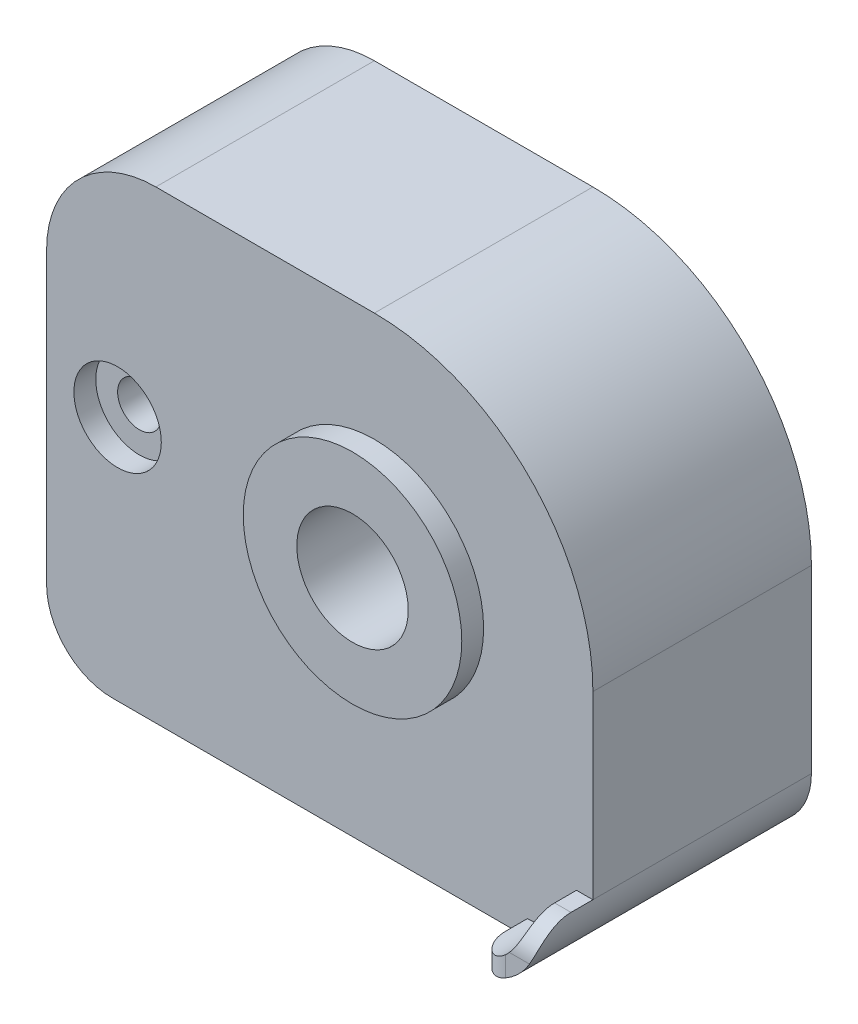
SolidWorks part; units mm, degrees
ref_plane "Plan de face" through (0, 0, 0) normal (0, 0, 1) x (1, 0, 0)
ref_plane "Plan de dessus" through (0, 0, 0) normal (0, 1, 0) x (1, 0, 0)
ref_plane "Plan de droite" through (0, 0, 0) normal (1, 0, 0) x (0, 0, -1)
sketch "Esquisse1" plane through (0, 0, 0) normal (0, 0, 1) x (1, 0, 0)
  line L0 (0, 20) -> (-30, 20)
  line L1 (-30, 20) -> (-30, -20)
  line L2 (-30, -20) -> (0, -20)
  line L3 (20, 0) -> (-30, 0) construction
  arc A0 (0, -20) -> (0, 20) centre (0, 0) ccw
  circle A1 centre (0, 0) radius 5.2
  circle A2 centre (-23.5, 0) radius 2
  circle A3 centre (-23.5, 0) radius 4
  dimension "D2" = 4
  dimension "D4" = 10.4
  dimension "D6" = 8
  dimension "D1" = 40
  dimension "D3" = 30
  dimension "D5" = 6.5
extrude "Boss.-Extru.1" add sketch "Esquisse1" along normal blind 20 contours L2 A0 L0 L1
sketch "Esquisse3" plane through (-30, 0, 0) normal (-1, 0, 0) x (0, 0, 1)
  line L0 (0, 0) -> (20, 0) construction
  line L1 (20, 20) -> (20, -20) construction
  circle A0 centre (10, 0) radius 5
  dimension "D1" = 10
  dimension "D2" = 10
extrude "Enlèv. mat.-Extru.1" cut sketch "Esquisse3" against normal blind 20
fillet "Congé1" radius 10 2 edges at (-30, 20, 10) (-30, -20, 10)
extrude "Enlèv. mat.-Extru.3" cut sketch "Esquisse1<4>" against normal through all and the other way through all contours A2
sketch "Esquisse1<4>" plane through (0, 0, 0) normal (0, 0, 1) x (1, 0, 0) same geometry as "Esquisse1"
extrude "Enlèv. mat.-Extru.4" cut sketch "Esquisse1<5>" along normal blind 2 contours A3
sketch "Esquisse1<5>" plane through (0, 0, 0) normal (0, 0, 1) x (1, 0, 0) same geometry as "Esquisse1"
extrude "Enlèv. mat.-Extru.5" cut sketch "Esquisse1<6>" against normal blind 2 from surface contours A3 starting at face at (-21.5, 0, 20)
sketch "Esquisse1<6>" plane through (0, 0, 0) normal (0, 0, 1) x (1, 0, 0) same geometry as "Esquisse1"
sketch "Esquisse5" plane through (0, 0, 20) normal (0, 0, 1) x (1, 0, 0)
  line L9 (20, 0) -> (20, -16.5)
  line L10 (14, -22.5) -> (-24, -22.5)
  line L11 (-30, -16.5) -> (-30, -10)
  line L12 (-20, -20) -> (0, -20)
  arc A3 (0, -20) -> (0, 20) centre (0, 0) ccw construction
  arc A6 (20, 0) -> (0, -20) centre (0, 0) cw
  arc A7 (20, -16.5) -> (14, -22.5) centre (14, -16.5) cw
  arc A8 (-24, -22.5) -> (-30, -16.5) centre (-24, -16.5) cw
  arc A9 (-30, -10) -> (-20, -20) centre (-20, -10) ccw
  point P0 (0, 0)
  dimension "D4" = 6
  dimension "D5" = 6
  dimension "D6" = 2.5
extrude "Boss.-Extru.4" add sketch "Esquisse5" against normal up to surface (20 mm away) up to face at (-19.5, 0, 0)
sketch "Esquisse6" plane through (0, 0, 20) normal (0, 0, 1) x (1, 0, 0)
  line L6 (20, -16.5) -> (18.5, -16.5)
  line L7 (14, -22.5) -> (14, -21)
  arc A4 (14, -22.5) -> (20, -16.5) centre (14, -16.5) ccw
  arc A5 (18.5, -16.5) -> (14, -21) centre (14, -16.5) cw
  point P0 (0, 0)
  dimension "D4" = 1.5
extrude "Boss.-Extru.5" add sketch "Esquisse6" along normal blind 5
fillet "Congé3" radius 3 1 edges at (14, -21.75, 25) first distance on face at (14, -21.75, 22.5)
fillet "Congé4" radius 3 1 edges at (19.25, -16.5, 25) first distance on face at (19.25, -16.5, 22.5)
sketch "Esquisse7" plane through (0, 0, 20) normal (0, 0, 1) x (1, 0, 0)
  line L2 (20, -16.5) -> (20, 0) construction
  line L3 (-24, -22.5) -> (14, -22.5) construction
  circle A0 centre (0, 0) radius 5.1
  dimension "D1" = 10.2
  dimension "D2" = 20
  dimension "D3" = 22.5
extrude "Enlèv. mat.-Extru.6" cut sketch "Esquisse7" against normal through all and the other way blind 2
sketch "Esquisse8" plane through (0, 0, 20) normal (0, 0, 1) x (1, 0, 0)
  line L5 (-30, 10) -> (-30, -16.5) construction
  line L6 (-20, 20) -> (0, 20)
  line L7 (20, 0) -> (20, -16.5)
  line L8 (14, -22.5) -> (-24, -22.5)
  line L9 (-30, -16.5) -> (-30, 10)
  arc A10 (-30, 10) -> (-20, 20) centre (-20, 10) cw
  arc A11 (-20, 20) -> (-30, 10) centre (-20, 10) ccw construction
  arc A12 (0, 20) -> (20, 0) centre (0, 0) cw
  arc A13 (20, -16.5) -> (14, -22.5) centre (14, -16.5) cw
  arc A14 (-24, -22.5) -> (-30, -16.5) centre (-24, -16.5) cw
sketch "Esquisse9" plane through (0, 0, 20) normal (0, 0, 1) x (1, 0, 0)
  circle A0 centre (0, 0) radius 10
  circle A1 centre (0, 0) radius 5.1 construction
  circle A2 centre (0, 0) radius 5.1
  dimension "D1" = 20
extrude "Boss.-Extru.7" add sketch "Esquisse9" along normal blind 2
